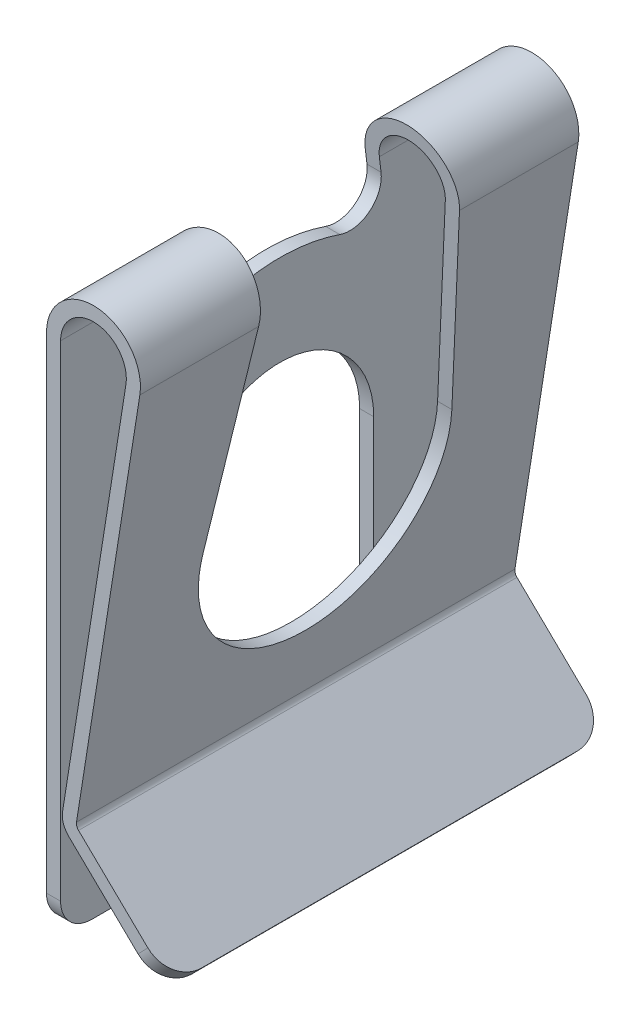
SolidWorks part; units mm, degrees
ref_plane "Front Plane" through (0, 0, 0) normal (0, 0, 1) x (1, 0, 0)
ref_plane "Top Plane" through (0, 0, 0) normal (0, 1, 0) x (1, 0, 0)
ref_plane "Right Plane" through (0, 0, 0) normal (1, 0, 0) x (0, 0, -1)
ref_plane "Plane1" through (0, 0, 0) normal (0, 0, 1) x (1, 0, 0)
sketch "Sketch1" plane through (0, 0, 0) normal (0, 0, 1) x (1, 0, 0)
  line L0 (0, 7.1) -> (0, -9.4)
  line L1 (0, -9.4) -> (0.45, -9.4)
  line L2 (0.45, -9.4) -> (0.45, 7.1)
  line L3 (2.5372, 6.9364) -> (0.514, -5.8881)
  line L4 (0.7114, -6.4784) -> (3.6433, -9.3149)
  line L5 (3.6433, -9.3149) -> (3.9562, -8.9915)
  line L6 (3.9562, -8.9915) -> (1.0243, -6.155)
  line L7 (0.9585, -5.9582) -> (2.9817, 6.8662)
  arc A0 (0.45, 7.1) -> (2.5372, 6.9364) centre (1.5, 7.1) cw
  arc A1 (0.514, -5.8881) -> (0.7114, -6.4784) centre (1.1807, -5.9933) ccw
  arc A2 (1.0243, -6.155) -> (0.9585, -5.9582) centre (1.1807, -5.9933) cw
  arc A3 (2.9817, 6.8662) -> (0, 7.1) centre (1.5, 7.1) ccw
extrude "Boss-Extrude1" add sketch "Sketch1" against normal blind 7 and the other way blind 7
ref_plane "Plane2" through (0, 0, 0) normal (1, 0, 0) x (0, 0, -1)
sketch "Sketch2" plane through (0, 0, 0) normal (1, 0, 0) x (0, 0, -1)
  line L0 (-3, 0) -> (-3, -9.4)
  line L1 (-3, -9.4) -> (3, -9.4)
  line L2 (3, -9.4) -> (3, 0)
  arc A0 (3, 0) -> (-3, 0) centre (0, 0) ccw
extrude "Cut-Extrude1" cut sketch "Sketch2" along normal blind 0.45
ref_plane "Plane3" through (0.45, 0, 0) normal (1, 0, 0) x (0, 0, -1)
sketch "Sketch3" plane through (0.45, 0, 0) normal (1, 0, 0) x (0, 0, -1)
  line L0 (3.9717, 0.475) -> (3, 8.6)
  line L1 (3, 8.6) -> (-3, 8.6)
  line L2 (-3, 8.6) -> (-3.9717, 0.475)
  arc A0 (-3.9717, 0.475) -> (3.9717, 0.475) centre (0, 0) ccw
extrude "Cut-Extrude2" cut sketch "Sketch3" along normal blind 3.9
ref_plane "Plane4" through (0.45, 0, 0) normal (1, 0, 0) x (0, 0, -1)
sketch "Sketch4" plane through (0.45, 0, 0) normal (1, 0, 0) x (0, 0, -1)
  line L0 (3.2338, 6.6447) -> (3, 8.6)
  line L1 (3, 8.6) -> (-3, 8.6)
  line L2 (-3, 8.6) -> (-3.2338, 6.6447)
  arc A0 (-3.2338, 6.6447) -> (-1.9161, 5.5802) centre (-2.2409, 6.526) ccw
  arc A1 (-1.9161, 5.5802) -> (1.9161, 5.5802) centre (0, 0) cw
  arc A2 (1.9161, 5.5802) -> (3.2338, 6.6447) centre (2.2409, 6.526) ccw
extrude "Cut-Extrude3" cut sketch "Sketch4" against normal blind 3.9
ref_plane "Plane5" through (0, 0, 0) normal (1, 0, 0) x (0, 0, -1)
sketch "Sketch5" plane through (0, 0, 0) normal (1, 0, 0) x (0, 0, -1)
  line L0 (-7, -9.4) -> (-6, -9.4)
  line L1 (-7, -8.4) -> (-7, -9.4)
  arc A0 (-6, -9.4) -> (-7, -8.4) centre (-6, -8.4) cw
extrude "Cut-Extrude4" cut sketch "Sketch5" along normal blind 0.45
ref_plane "Plane6" through (0, 0, 0) normal (1, 0, 0) x (0, 0, -1)
sketch "Sketch6" plane through (0, 0, 0) normal (1, 0, 0) x (0, 0, -1)
  line L0 (6, -9.4) -> (7, -9.4)
  line L1 (7, -9.4) -> (7, -8.4)
  arc A0 (7, -8.4) -> (6, -9.4) centre (6, -8.4) cw
extrude "Cut-Extrude5" cut sketch "Sketch6" along normal blind 0.45
ref_plane "Plane7" through (0, 0, 0) normal (1, 0, 0) x (0, 0, -1)
sketch "Sketch7" plane through (0, 0, 0) normal (1, 0, 0) x (0, 0, -1)
  line L0 (3, -9.4) -> (3.5, -9.4)
  line L1 (3, -8.9) -> (3, -9.4)
  arc A0 (3.5, -9.4) -> (3, -8.9) centre (3.5, -8.9) cw
extrude "Cut-Extrude6" cut sketch "Sketch7" along normal blind 0.45
ref_plane "Plane8" through (0, 0, 0) normal (1, 0, 0) x (0, 0, -1)
sketch "Sketch8" plane through (0, 0, 0) normal (1, 0, 0) x (0, 0, -1)
  line L0 (-3.5, -9.4) -> (-3, -9.4)
  line L1 (-3, -9.4) -> (-3, -8.9)
  arc A0 (-3, -8.9) -> (-3.5, -9.4) centre (-3.5, -8.9) cw
extrude "Cut-Extrude7" cut sketch "Sketch8" along normal blind 0.45
ref_plane "Plane9" through (-2.5806, -2.6674, 0) normal (0.6953, 0.7187, 0) x (0.7187, -0.6953, 0)
sketch "Sketch9" plane through (-2.5806, -2.6674, 0) normal (0.6953, 0.7187, 0) x (0.7187, -0.6953, 0)
  line L0 (8.0948, -7) -> (8.0948, -8)
  line L1 (8.0948, -8) -> (10.0948, -8)
  line L2 (10.0948, -8) -> (10.0948, 8)
  line L3 (10.0948, 8) -> (8.0948, 8)
  line L4 (8.0948, 8) -> (8.0948, 7)
  line L5 (9.0948, 6) -> (9.0948, -6)
  arc A0 (8.0948, 7) -> (9.0948, 6) centre (8.0948, 6) cw
  arc A1 (9.0948, -6) -> (8.0948, -7) centre (8.0948, -6) cw
extrude "Cut-Extrude8" cut sketch "Sketch9" against normal blind 0.9 and the other way blind 0.9
